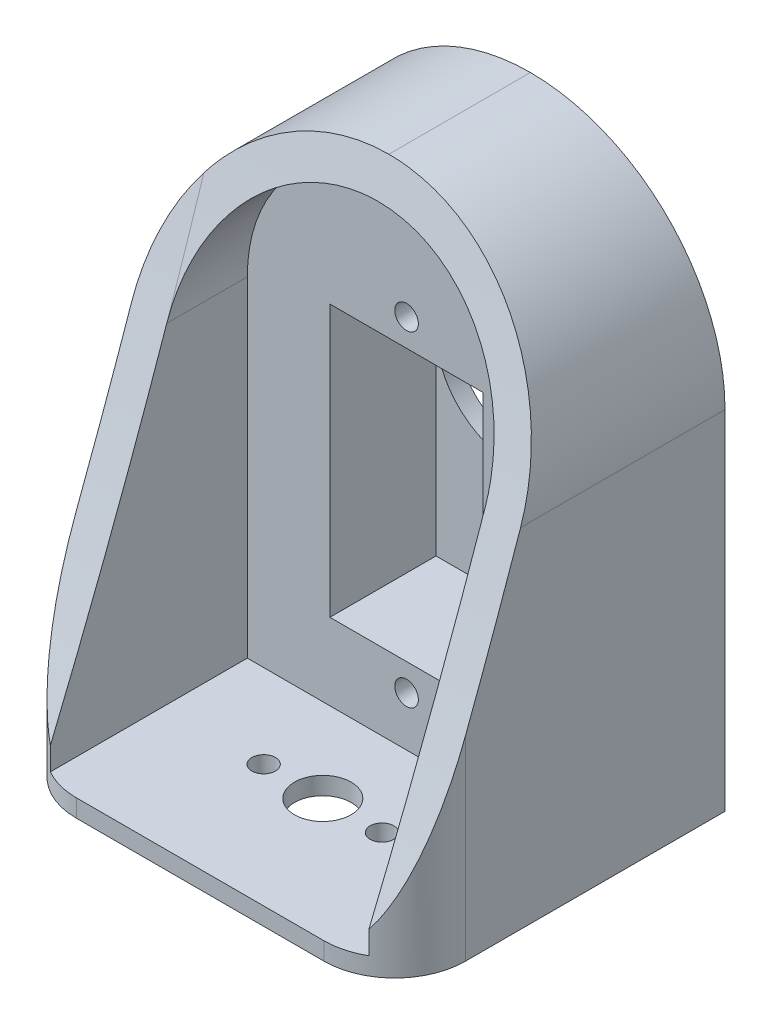
SolidWorks part; units mm, degrees
ref_plane "Front Plane" through (0, 0, 0) normal (0, 0, 1) x (1, 0, 0)
ref_plane "Top Plane" through (0, 0, 0) normal (0, 1, 0) x (1, 0, 0)
ref_plane "Right Plane" through (0, 0, 0) normal (1, 0, 0) x (0, 0, -1)
sketch "Sketch1" plane through (0, 0, 0) normal (0, 1, 0) x (1, 0, 0)
  line L1 (-16.5, -14) -> (16.5, -14)
  line L2 (-16.5, -14) -> (-16.5, 14)
  line L3 (-16.5, 14) -> (16.5, 14)
  line L4 (16.5, -14) -> (16.5, 14)
  line L5 (-16.5, -14) -> (16.5, 14) construction
  line L6 (-16.5, 14) -> (16.5, -14) construction
  point P0 (0, 0)
  dimension "D1" = 33
  dimension "D2" = 28
extrude "Boss-Extrude1" add sketch "Sketch1" along normal blind 46
sketch "Sketch3" plane through (16.5, 0, 0) normal (1, 0, 0) x (0, 0, -1)
  line L2 (-14, 0) -> (14, 0) construction
  line L3 (14, 46) -> (11.5, 46)
  line L4 (14, 46) -> (14, 21)
  line L5 (14, 21) -> (11.5, 21)
  line L6 (11.5, 46) -> (11.5, 21)
  line L7 (-14, 46) -> (3.5, 46)
  line L8 (-14, 46) -> (-14, 1.5)
  line L9 (-14, 1.5) -> (3.5, 1.5)
  line L10 (3.5, 46) -> (3.5, 1.5)
  line M11 (14, 46) -> (-14, 46)
  line M12 (-14, 46) -> (-14, 0)
  dimension "D1" = 1.5
  dimension "D2" = 8
  dimension "D3" = 2.5
  dimension "D4" = 25
extrude "Cut-Extrude2" cut sketch "Sketch3" against normal through all contours L10 L9 M11 M12 region at (16.5, 23.75, 5.25)
sketch "Sketch5" plane through (16.5, 0, 0) normal (1, 0, 0) x (0, 0, -1)
  line L0 (3.5, 46) -> (2, 46)
  line L1 (3.5, 46) -> (3.5, 1.5)
  line L2 (3.5, 1.5) -> (-14, 1.5)
  spline S0 degree 2 poles (2, 46) (-4.8571, 23.3254) (-14, 1.5) knots 0 0 0 1 1 1
  dimension "D1" = 1.5
extrude "Boss-Extrude2" add sketch "Sketch5" against normal blind 3
sketch "Sketch6" plane through (-16.5, 0, 0) normal (-1, 0, 0) x (0, 0, 1)
  line L3 (-2, 46) -> (-3.5, 46)
  line L4 (-3.5, 46) -> (-3.5, 1.5)
  line L5 (-3.5, 1.5) -> (14, 1.5)
  line L6 (-2, 46) -> (-3.5, 46)
  line L7 (-3.5, 46) -> (-3.5, 1.5)
  line L8 (-3.5, 1.5) -> (14, 1.5)
  parabola Q1 (14, 1.5) -> (-2, 46) focus (221.9743, 98.8362) apex (7.0828, 19.0115)
  parabola Q2 (14, 1.5) -> (-2, 46) focus (221.9743, 98.8362) apex (7.0828, 19.0115)
  dimension "D1" = 0
extrude "Boss-Extrude3" add sketch "Sketch6" against normal blind 3
sketch "Sketch8" plane through (13.5, 0, 0) normal (-1, 0, 0) x (0, 0, 1)
  line L0 (-3.5, 43) -> (-1.0816, 43)
  line L1 (-3.5, 1.5) -> (-3.5, 46) construction
  line L2 (-3.5, 46) -> (-2, 46) construction
  line L6 (-2, 46) -> (-3.5, 46)
  line L7 (-3.5, 46) -> (-3.5, 1.5)
  line L8 (-3.5, 1.5) -> (14, 1.5)
  line L9 (-2, 46) -> (-3.5, 46)
  line L10 (-3.5, 46) -> (-3.5, 1.5)
  line L11 (-3.5, 1.5) -> (14, 1.5)
  parabola Q0 (-2, 46) -> (14, 1.5) focus (221.9743, 98.8362) apex (7.0828, 19.0115) construction
  parabola Q2 (14, 1.5) -> (-2, 46) focus (221.9743, 98.8362) apex (7.0828, 19.0115)
  parabola Q3 (14, 1.5) -> (-2, 46) focus (221.9743, 98.8362) apex (7.0828, 19.0115)
  spline M2 degree 2 poles (-2, 46) (4.8571, 23.3254) (14, 1.5) knots 0 0 0 1 1 1
  line M3 (-2, 46) -> (-3.5, 46)
  line M4 (-3.5, 46) -> (-3.5, 1.5)
  dimension "D1" = 3
  dimension "D2" = 0
extrude "Boss-Extrude4" add sketch "Sketch8" along normal up to surface (27 mm away) contours L0 M4 M2 M3 region at (13.5, 44.3827, -2.5034) up to face at (-13.5, 18.1875, 1.0625)
fillet "Fillet2" radius 13.5 2 edges
fillet "Fillet3" radius 16.5 2 edges at (-16.5, 46, -8) (16.5, 46, -8)
sketch "Sketch9" plane through (0, 0, -3.5) normal (0, 0, 1) x (1, 0, 0)
  line L0 (-13.5, 1.5) -> (13.5, 1.5) construction
  line L1 (-6.5, 8) -> (6.5, 8)
  line L2 (-6.5, 8) -> (-6.5, 31)
  line L3 (-6.5, 31) -> (6.5, 31)
  line L4 (6.5, 8) -> (6.5, 31)
  line L5 (-6.5, 8) -> (6.5, 31) construction
  line L6 (-6.5, 31) -> (6.5, 8) construction
  point P0 (0, 19.5)
  dimension "D1" = 13
  dimension "D2" = 23
  dimension "D3" = 6.5
sketch "Sketch18" plane through (0, 1.5, 0) normal (0, 1, 0) x (1, 0, 0)
  line L0 (0, 2) -> (0, 14) construction
  circle A0 centre (0, -3.5999) radius 2.4
  circle A1 centre (5.0159, -3.5999) radius 1
  circle A2 centre (-5.0159, -3.5999) radius 1
extrude "Cut-Extrude10" cut sketch "Sketch18" against normal through all
extrude "Cut-Extrude4" cut sketch "Sketch9" against normal blind 9
sketch "Sketch10" plane through (0, 0, -12.5) normal (0, 0, 1) x (1, 0, 0)
  line L1 (6.5, 31) -> (-6.5, 31) construction
  circle A0 centre (0, 24.5) radius 6.5
  dimension "D1" = 13
  dimension "D2" = 6.5
extrude "Cut-Extrude5" cut sketch "Sketch10" against normal through all
sketch "Sketch11" plane through (0, 0, -3.5) normal (0, 0, 1) x (1, 0, 0)
  line L1 (6.5, 31) -> (0, 31) construction
  circle A0 centre (0, 33.3) radius 1
  circle A1 centre (0, 5.7) radius 1
  dimension "D1" = 27.6
  dimension "D2" = 2
  dimension "D3" = 2
  dimension "D4" = 2.3
extrude "Cut-Extrude6" cut sketch "Sketch11" against normal blind 8
fillet "Fillet4" radius 6 2 edges at (-16.5, 0.75, 14) (16.5, 0.75, 14)
